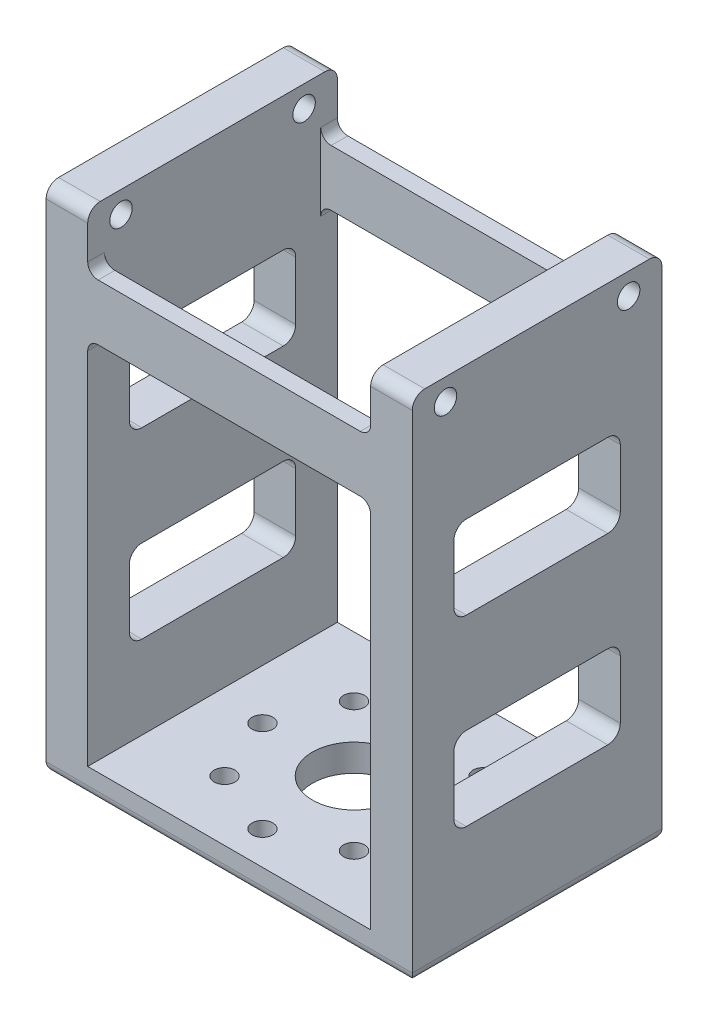
SolidWorks part; units mm, degrees
ref_plane "Front Plane" through (0, 0, 0) normal (0, 0, 1) x (1, 0, 0)
ref_plane "Top Plane" through (0, 0, 0) normal (0, 1, 0) x (1, 0, 0)
ref_plane "Right Plane" through (0, 0, 0) normal (1, 0, 0) x (0, 0, -1)
sketch "Sketch1" plane through (0, 0, 0) normal (0, 1, 0) x (1, 0, 0)
  line L1 (0, 0) -> (44, 0)
  line L2 (0, 0) -> (0, 30)
  line L3 (0, 30) -> (44, 30)
  line L4 (44, 0) -> (44, 30)
  dimension "D1" = 30
  dimension "D2" = 44
extrude "Boss-Extrude1" add sketch "Sketch1" along normal blind 54.5
sketch "Sketch5" plane through (0, 54.5, 0) normal (0, 1, 0) x (1, 0, 0)
  line L0 (0, 0) -> (44, 0) construction
  line L1 (0, 30) -> (5, 30)
  line L2 (0, 30) -> (0, 0)
  line L3 (0, 0) -> (5, 0)
  line L4 (5, 30) -> (5, 0)
  dimension "D1" = 5
ref_plane "Plane1" through (22, 0, 0) normal (-1, 0, 0) x (0, 0, 1)
extrude "Boss-Extrude3" add sketch "Sketch5" along normal blind 6.8
sketch "Sketch9" plane through (5, 0, 0) normal (1, 0, 0) x (0, 0, -1)
  line L0 (30, 61.3) -> (30, 54.5) construction
  line L2 (0, 61.3) -> (0, 54.5) construction
  line L4 (0, 61.3) -> (30, 61.3) construction
  circle A0 centre (26, 58.7) radius 1.35
  circle A1 centre (4, 58.7) radius 1.35
  dimension "D1" = 2.7
  dimension "D2" = 4
  dimension "D3" = 2.6
  dimension "D4" = 2.7
  dimension "D5" = 4
  dimension "D6" = 2.6
extrude "Cut-Extrude6" cut sketch "Sketch9" against normal through all
mirror "Mirror2" about plane through (22, 0, 0) normal (-1, 0, 0) of "Boss-Extrude3", "Cut-Extrude6"
fillet "Fillet1" radius 1.5 4 edges at (41.5, 61.3, -30) (2.5, 61.3, -30) (2.5, 61.3, 0) (41.5, 61.3, 0)
fillet "Fillet2" radius 1.25 4 edges at (0, 0, -15) (22, 0, -30) (22, 0, 0) (44, 0, -15)
sketch "Sketch11" plane through (0, 54.5, 0) normal (0, 1, 0) x (1, 0, 0)
  line L0 (39, 0) -> (39, 30) construction
  line L1 (39, 28) -> (5, 28)
  line L2 (39, 28) -> (39, 2)
  line L3 (39, 2) -> (5, 2)
  line L4 (5, 28) -> (5, 2)
  line L5 (5, 0) -> (5, 30) construction
  line L6 (39, 30) -> (5, 30) construction
  line L7 (5, 0) -> (39, 0) construction
  dimension "D1" = 2
  dimension "D2" = 2
extrude "Cut-Extrude7" cut sketch "Sketch11" against normal blind 51.25
ref_point "Point1"
sketch "Sketch13" plane through (0, 0, 0) normal (0, -1, 0) x (1, 0, 0)
  circle A0 centre (22, -15) radius 5
  circle A1 centre (33, -15) radius 1.25
  dimension "D1" = 10
  dimension "D2" = 2.5
  dimension "D3" = 11
extrude "Cut-Extrude8" cut sketch "Sketch13" against normal up to next
ref_axis "Axis1" through (22, 0, -15) along (0, -1, 0)
pattern_circular "CirPattern1" count 8 over 360 about axis through (22, 0, -15) along (0, -1, 0) of "Cut-Extrude8"
ref_plane "Plane2" through (0, 0, -15) normal (0, 0, -1) x (-1, 0, 0)
sketch "Sketch15" plane through (44, 0, 0) normal (1, 0, 0) x (0, 0, -1)
  line L0 (0, 1.25) -> (30, 1.25) construction
  line L1 (25, 13.25) -> (5, 13.25)
  line L2 (25, 13.25) -> (25, 23.25)
  line L3 (25, 23.25) -> (5, 23.25)
  line L4 (5, 13.25) -> (5, 23.25)
  line L5 (30, 59.8) -> (30, 1.25) construction
  line L6 (0, 59.8) -> (0, 1.25) construction
  line L8 (25, 35.25) -> (5, 35.25)
  line L9 (25, 35.25) -> (25, 45.25)
  line L10 (25, 45.25) -> (5, 45.25)
  line L11 (5, 35.25) -> (5, 45.25)
  dimension "D1" = 12
  dimension "D2" = 10
  dimension "D3" = 5
  dimension "D4" = 5
  dimension "D5" = 12
  dimension "D6" = 10
extrude "Cut-Extrude10" cut sketch "Sketch15" against normal up to next
fillet "Fillet6" radius 1.5 8 edges at (41.5, 13.25, -5) (41.5, 35.25, -5) (41.5, 23.25, -5) (41.5, 45.25, -5) (41.5, 23.25, -25) (41.5, 45.25, -25) (41.5, 35.25, -25) (41.5, 13.25, -25)
mirror "Mirror4" about plane through (22, 0, 0) normal (-1, 0, 0) of "Cut-Extrude10", "Fillet6"
sketch "Sketch16" plane through (0, 0, 0) normal (0, 0, 1) x (1, 0, 0)
  line L0 (42.75, 0) -> (1.25, 0) construction
  line L1 (5, 47.75) -> (39, 47.75)
  line L2 (5, 47.75) -> (5, 3.25)
  line L3 (5, 3.25) -> (39, 3.25)
  line L4 (39, 47.75) -> (39, 3.25)
  line L6 (5, 54.5) -> (39, 54.5) construction
  dimension "D1" = 3.25
  dimension "D2" = 6.75
extrude "Cut-Extrude11" cut sketch "Sketch16" against normal up to next
mirror "Mirror5" about plane through (0, 0, -15) normal (0, 0, -1) of "Cut-Extrude11"
fillet "Fillet7" radius 1.25 8 edges at (5, 47.75, -29) (5, 47.75, -1) (5, 54.5, -1) (5, 54.5, -29) (39, 54.5, -1) (39, 54.5, -29) (39, 47.75, -29) (39, 47.75, -1)
